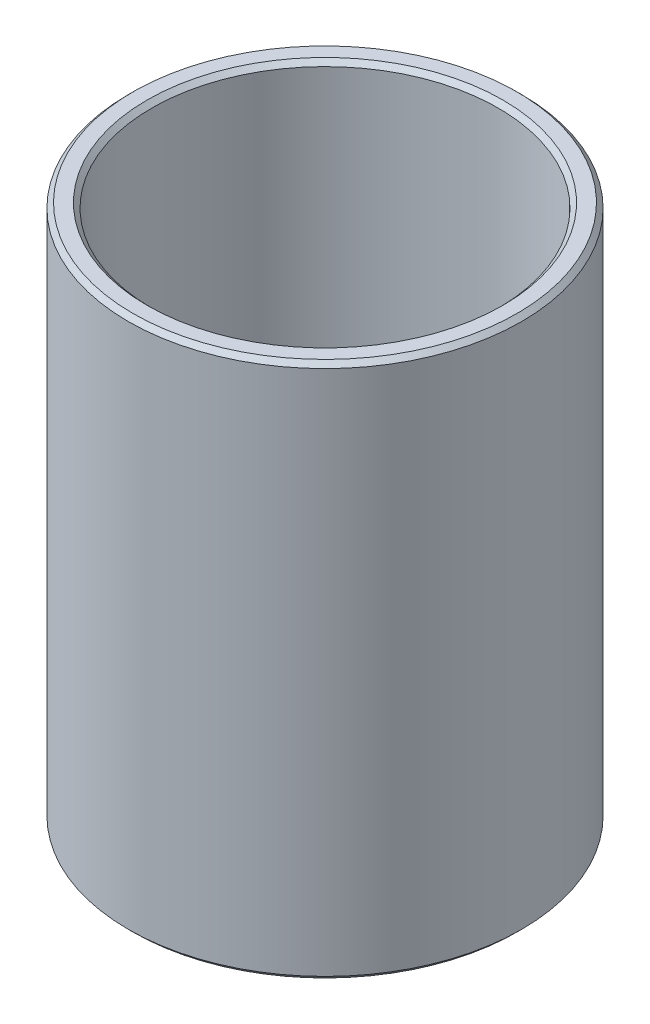
SolidWorks part; units mm, degrees
ref_plane "Front Plane" through (0, 0, 0) normal (0, 0, 1) x (1, 0, 0)
ref_plane "Top Plane" through (0, 0, 0) normal (0, 1, 0) x (1, 0, 0)
ref_plane "Right Plane" through (0, 0, 0) normal (1, 0, 0) x (0, 0, -1)
sketch "Sketch1" plane through (0, 0, 0) normal (0, 1, 0) x (1, 0, 0)
  circle A0 centre (0, 0) radius 52.5
  dimension "SLEEVE_OD" = 105
extrude "Boss-Extrude1" add sketch "Sketch1" along normal blind 143.0274
sketch "Sketch2" plane through (0, 0, 0) normal (0, 1, 0) x (1, 0, 0)
  circle A0 centre (0, 0) radius 46.2569
  dimension "BORE_D" = 92.5138
extrude "Cut-Extrude1" cut sketch "Sketch2" along normal through all
chamfer "Chamfer1" distance 1.2422 angle 45 4 edges at (0, 143.0274, 46.2569) (0, 0, 46.2569) (0, 0, 52.5) (0, 143.0274, 52.5)
